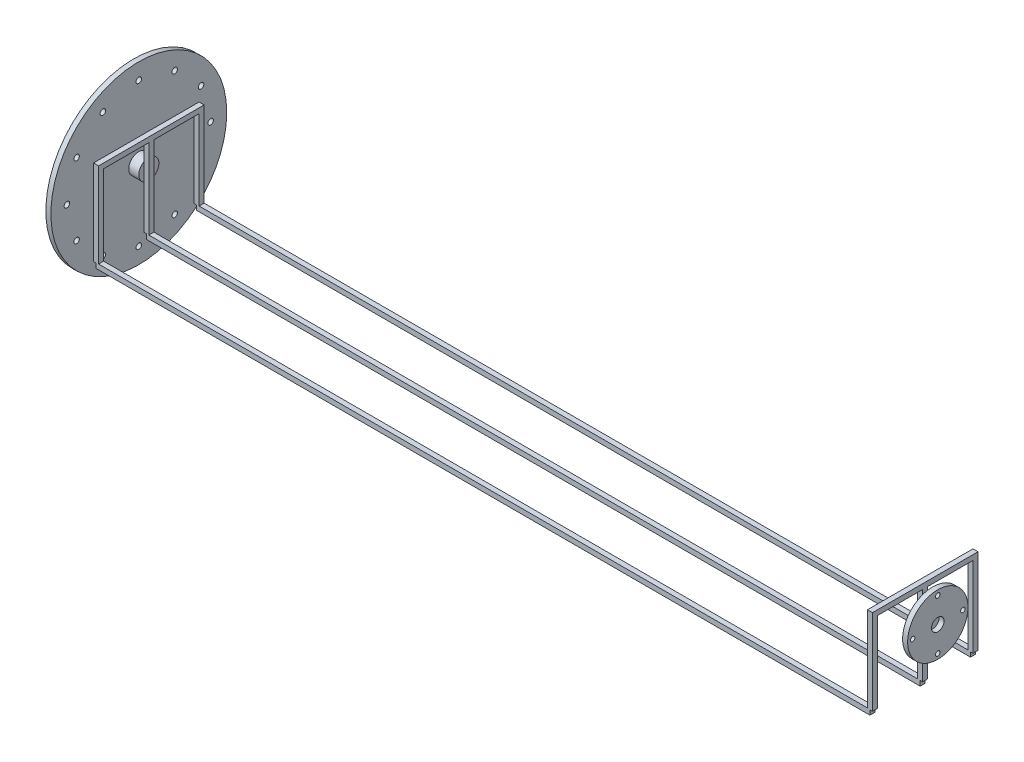
SolidWorks part; units mm, degrees
ref_plane "前视基准面" through (0, 0, 0) normal (0, 0, 1) x (1, 0, 0)
ref_plane "上视基准面" through (0, 0, 0) normal (0, 1, 0) x (1, 0, 0)
ref_plane "右视基准面" through (0, 0, 0) normal (1, 0, 0) x (0, 0, -1)
sketch "草图1" plane through (0, 0, 0) normal (1, 0, 0) x (0, 0, -1)
  line L0 (0, 0) -> (-227.1212, 0) construction
  circle A0 centre (0, 0) radius 175
  circle A1 centre (0, 0) radius 143 construction
  circle A2 centre (-143, 0) radius 5.5
  circle A3 centre (-123.8416, 71.5) radius 5.5
  circle A4 centre (-71.5, 123.8416) radius 5.5
  circle A5 centre (0, 143) radius 5.5
  circle A6 centre (71.5, 123.8416) radius 5.5
  circle A7 centre (123.8416, 71.5) radius 5.5
  circle A8 centre (143, 0) radius 5.5
  circle A9 centre (123.8416, -71.5) radius 5.5
  circle A10 centre (71.5, -123.8416) radius 5.5
  circle A11 centre (0, -143) radius 5.5
  circle A12 centre (-71.5, -123.8416) radius 5.5
  circle A13 centre (-123.8416, -71.5) radius 5.5
  point P32 (0, 0)
  dimension "D1" = 350
  dimension "D2" = 286
  dimension "D3" = 11
  dimension "D4" = 12
extrude "凸台-拉伸1" add sketch "草图1" along normal blind 10
sketch "草图2" plane through (10, 0, 0) normal (1, 0, 0) x (0, 0, -1)
  circle A0 centre (0, 0) radius 20
  dimension "D1" = 40
extrude "凸台-拉伸2" add sketch "草图2" against normal blind 30
extrude "凸台-拉伸3" add sketch "草图2<2>" along normal blind 20
sketch "草图2<2>" plane through (10, 0, 0) normal (1, 0, 0) x (0, 0, -1) same geometry as "草图2"
sketch "草图3" plane through (30, 0, 0) normal (1, 0, 0) x (0, 0, -1)
  line L0 (0, 65.4776) -> (0, -103.7724)
extrude "拉伸-薄壁1" add sketch "草图3" along normal blind 10 thin thin type one direction wall 10
sketch "草图4" plane through (0, 0, 0) normal (0, 0, 1) x (1, 0, 0)
  line L0 (35, -103.7724) -> (1575, -103.7724)
  line L1 (40, -103.7724) -> (30, -103.7724) construction
  dimension "D1" = 1540
extrude "拉伸-薄壁2" add sketch "草图4" along normal blind 10 thin thin type one direction wall 10
pattern_linear "阵列(线性)1" count 2 spacing 1540 along (1, 0, 0) of "拉伸-薄壁1"
pattern_linear "阵列(线性)2" count 2 spacing 1560 along (1, 0, 0) of "凸台-拉伸3"
sketch "草图5" plane through (1590, 0, 0) normal (1, 0, 0) x (0, 0, -1)
  circle A0 centre (0, 0) radius 60
  dimension "D1" = 120
extrude "凸台-拉伸4" add sketch "草图5" along normal blind 10
sketch "草图6" plane through (1600, 0, 0) normal (1, 0, 0) x (0, 0, -1)
  line L0 (0, 21.51) -> (0, 83.9138) construction
  circle A0 centre (0, 0) radius 50 construction
  circle A1 centre (0, 50) radius 4.5
  circle A2 centre (50, 0) radius 4.5
  circle A3 centre (0, -50) radius 4.5
  circle A4 centre (-50, 0) radius 4.5
  point P17 (0, 0)
  dimension "D1" = 100
  dimension "D2" = 9
  dimension "D3" = 4
extrude "切除-拉伸2" cut sketch "草图6" against normal up to next
sketch "草图7" plane through (1600, 0, 0) normal (1, 0, 0) x (0, 0, -1)
  circle A0 centre (0, 0) radius 12.5
  dimension "D1" = 25
extrude "切除-拉伸3" cut sketch "草图7" against normal blind 10
sketch "草图8" plane through (30, 0, 0) normal (1, 0, 0) x (0, 0, -1)
  line L0 (-100, 65.4776) -> (100, 65.4776)
  line L1 (0, 95.6063) -> (0, 21.5451) construction
  dimension "D1" = 200
  dimension "D2" = 100
extrude "拉伸-薄壁3" add sketch "草图8" along normal blind 10 thin thin type one direction wall 10
pattern_linear "阵列(线性)4" count 2 spacing 1540 along (1, 0, 0) of "拉伸-薄壁3"
sketch "草图9" plane through (30, 0, 0) normal (1, 0, 0) x (0, 0, -1)
  line L0 (100, 65.4776) -> (100, -104.5224)
  dimension "D2" = 170
extrude "拉伸-薄壁4" add sketch "草图9" along normal blind 10 thin thin type one direction wall 10
pattern_linear "阵列(线性)6" count 2 spacing 100 along (0, 0, -1) of "拉伸-薄壁2"
pattern_linear "阵列(线性)7" count 2 spacing 1540 along (1, 0, 0) of "拉伸-薄壁4"
sketch "草图10" plane through (30, 0, 0) normal (1, 0, 0) x (0, 0, -1)
  line L0 (-100, 65.4776) -> (-100, -104.5224)
  dimension "D1" = 170
extrude "拉伸-薄壁5" add sketch "草图10" along normal blind 10 thin thin type one direction wall 10
pattern_linear "阵列(线性)8" count 2 spacing 100 along (0, 0, 1) of "拉伸-薄壁2"
pattern_linear "阵列(线性)9" count 2 spacing 1540 along (1, 0, 0) of "拉伸-薄壁5"
